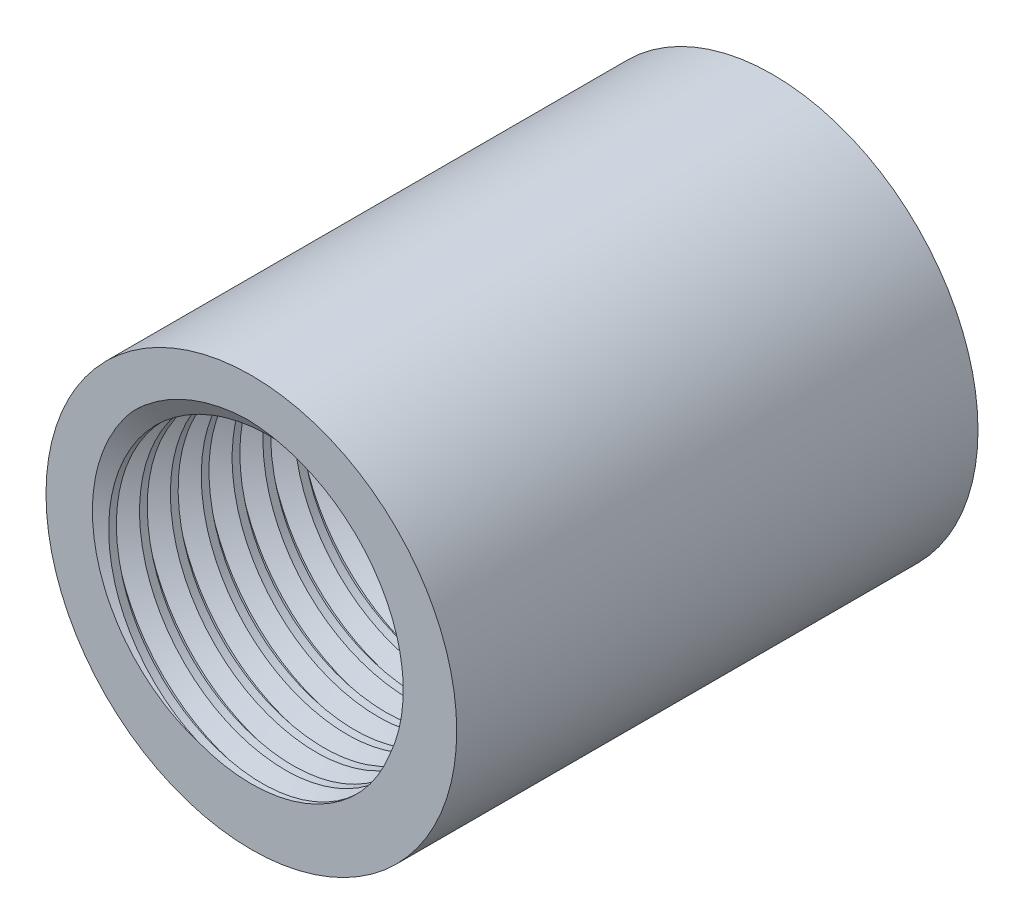
SolidWorks part; units mm, degrees
ref_plane "Płaszczyzna przednia" through (0, 0, 0) normal (0, 0, 1) x (1, 0, 0)
ref_plane "Płaszczyzna górna" through (0, 0, 0) normal (0, 1, 0) x (1, 0, 0)
ref_plane "Płaszczyzna prawa" through (0, 0, 0) normal (1, 0, 0) x (0, 0, -1)
sketch "Szkic1" plane through (0, 0, 0) normal (0, 0, 1) x (1, 0, 0)
  circle A0 centre (0, 0) radius 13
  circle A1 centre (0, 0) radius 9.4
  dimension "D1" = 26
  dimension "D2" = 18.8
extrude "Dodanie-wyciągnięcie1" add sketch "Szkic1" along normal blind 33
thread "Gwint1" pitch 1.9538 method cut trim with start face yes trim with end face yes profile "Profil gwintu1" start angle 0, offset 5, length 0, pitch 1.9538, diameter 18.8
ref_plane "Płaszczyzna1" through (-9.4, 0, 38) normal (0, -1, 0) x (-1, 0, 0)
sketch "Profil gwintu1" plane through (-9.4, 0, 38) normal (0, -1, 0) x (-1, 0, 0)
  line L0 (0, 0) -> (0, 1.9538) construction
  line L1 (0, 0) -> (1.0576, 0.6106)
  line L2 (1.0576, 0.6106) -> (1.0576, 0.8548)
  line L3 (1.0576, 0.8548) -> (0, 1.4654)
  line L4 (1.0576, 0.7327) -> (0, 0.7327) construction
  line L11 (0, 0) -> (0, 1.4654)
  point P2 (0, 0)
  dimension "Pitch" = 1.9538
  dimension "Profile_Angle" = 60
  dimension "Profile_Land" = 0.2442
  dimension "Profile_Height" = 1.0576
